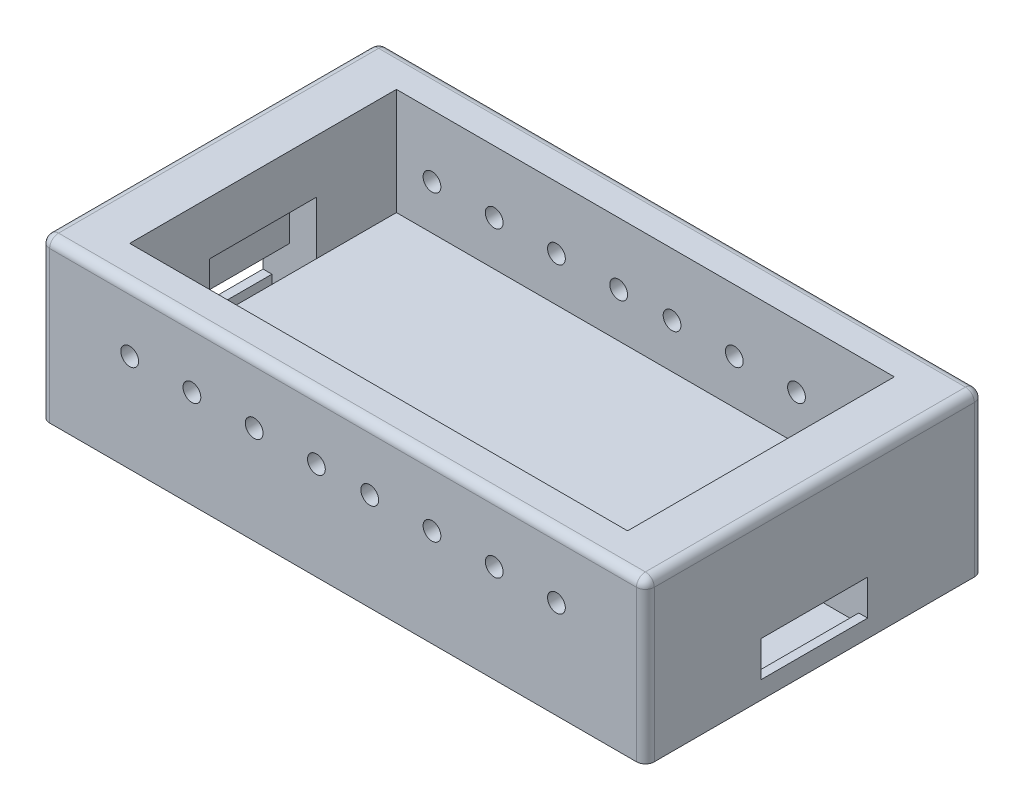
SolidWorks part; units mm, degrees
ref_plane "Front Plane" through (0, 0, 0) normal (0, 0, 1) x (1, 0, 0)
ref_plane "Top Plane" through (0, 0, 0) normal (0, 1, 0) x (1, 0, 0)
ref_plane "Right Plane" through (0, 0, 0) normal (1, 0, 0) x (0, 0, -1)
sketch "Sketch1" plane through (0, 0, 0) normal (0, 1, 0) x (1, 0, 0)
  line L1 (-711.2, 381) -> (711.2, 381)
  line L2 (-711.2, 381) -> (-711.2, -381)
  line L3 (-711.2, -381) -> (711.2, -381)
  line L4 (711.2, 381) -> (711.2, -381)
  line L5 (-863.6, 482.6) -> (863.6, 482.6)
  line L6 (-863.6, 482.6) -> (-863.6, -482.6)
  line L7 (-863.6, -482.6) -> (863.6, -482.6)
  line L8 (863.6, 482.6) -> (863.6, -482.6)
  point P4 (0, 381)
  point P8 (-711.2, 0)
  dimension "D1" = 762
  dimension "D2" = 1422.4
  dimension "D3" = 152.4
  dimension "D4" = 152.4
  dimension "D5" = 101.6
  dimension "D6" = 101.6
extrude "Boss-Extrude1" add sketch "Sketch1" along normal blind 457.2
sketch "Sketch2" plane through (0, 0, 0) normal (0, 1, 0) x (1, 0, 0)
  line L1 (-711.2, 381) -> (711.2, 381)
  line L2 (-711.2, 381) -> (-711.2, -381)
  line L3 (-711.2, -381) -> (711.2, -381)
  line L4 (711.2, 381) -> (711.2, -381)
extrude "Boss-Extrude2" add sketch "Sketch2" along normal blind 152.4
sketch "Sketch3" plane through (0, 152.4, 0) normal (0, 1, 0) x (1, 0, 0)
  line L0 (0, 381) -> (0, -381) construction
  line L1 (711.2, 381) -> (-711.2, 381) construction
  line L2 (-711.2, -381) -> (711.2, -381) construction
  circle A0 centre (0, 0) radius 152.4 construction
sketch "Sketch4" plane through (0, 0, 482.6) normal (0, 0, 1) x (1, 0, 0)
  line L0 (-863.6, 457.2) -> (-863.6, 0) construction
  line L1 (863.6, 457.2) -> (863.6, 0) construction
  line L2 (-863.6, 457.2) -> (863.6, 457.2) construction
  circle A0 centre (-609.6, 279.4) radius 25.4
  circle A1 centre (-431.8, 279.4) radius 25.4
  circle A2 centre (-254, 279.4) radius 25.4
  circle A3 centre (-76.2, 279.4) radius 25.4
  circle A4 centre (76.2, 279.4) radius 25.4
  circle A5 centre (254, 279.4) radius 25.4
  circle A6 centre (431.8, 279.4) radius 25.4
  circle A7 centre (609.6, 279.4) radius 25.4
  dimension "D9" = 50.8
  dimension "D10" = 50.8
  dimension "D11" = 50.8
  dimension "D12" = 50.8
  dimension "D13" = 50.8
  dimension "D14" = 50.8
  dimension "D15" = 50.8
  dimension "D16" = 50.8
  dimension "D1" = 254
  dimension "D2" = 254
  dimension "D3" = 431.8
  dimension "D4" = 431.8
  dimension "D5" = 609.6
  dimension "D6" = 609.6
  dimension "D7" = 787.4
  dimension "D8" = 787.4
  dimension "D17" = 177.8
extrude "Cut-Extrude1" cut sketch "Sketch4" against normal through all both and the other way through all
sketch "Sketch7" plane through (863.6, 0, 0) normal (1, 0, 0) x (0, 0, -1)
  line L1 (-152.4, 25.4) -> (152.4, 25.4)
  line L2 (-152.4, 25.4) -> (-152.4, 152.4)
  line L3 (-152.4, 152.4) -> (152.4, 152.4)
  line L4 (152.4, 25.4) -> (152.4, 152.4)
  line L6 (-482.6, 0) -> (482.6, 0) construction
  point P8 (0, 152.4)
  dimension "D1" = 304.8
  dimension "D2" = 127
  dimension "D3" = 25.4
extrude "Cut-Extrude2" cut sketch "Sketch7" against normal blind 127
sketch "Sketch8" plane through (0, 25.4, 0) normal (0, 1, 0) x (1, 0, 0)
  line L0 (711.2, -381) -> (711.2, 381) construction
  line L1 (711.2, 152.4) -> (787.4, 152.4)
  line L2 (711.2, 152.4) -> (711.2, -152.4)
  line L3 (711.2, -152.4) -> (787.4, -152.4)
  line L4 (787.4, 152.4) -> (787.4, -152.4)
  point P6 (787.4, 0)
  dimension "D1" = 304.8
  dimension "D2" = 76.2
extrude "Cut-Extrude3" cut sketch "Sketch8" along normal blind 304.8
sketch "Sketch9" plane through (0, 25.4, 0) normal (0, 1, 0) x (1, 0, 0)
  line L0 (863.6, -482.6) -> (863.6, 482.6) construction
  line L1 (863.6, 152.4) -> (838.2, 152.4)
  line L2 (863.6, 152.4) -> (863.6, -152.4)
  line L3 (863.6, -152.4) -> (838.2, -152.4)
  line L4 (838.2, 152.4) -> (838.2, -152.4)
  point P6 (838.2, 0)
  dimension "D1" = 304.8
  dimension "D2" = 25.4
extrude "Boss-Extrude3" add sketch "Sketch9" along normal blind 25.4
sketch "Sketch11" plane through (-863.6, 0, 0) normal (-1, 0, 0) x (0, 0, 1)
  line L0 (-482.6, 0) -> (482.6, 0) construction
  line L1 (-152.4, 25.4) -> (152.4, 25.4)
  line L2 (-152.4, 25.4) -> (-152.4, 152.4)
  line L3 (-152.4, 152.4) -> (152.4, 152.4)
  line L4 (152.4, 25.4) -> (152.4, 152.4)
  point P4 (0, 152.4)
  dimension "D1" = 127
  dimension "D2" = 304.8
  dimension "D3" = 25.4
extrude "Cut-Extrude5" cut sketch "Sketch11" against normal blind 127
sketch "Sketch13" plane through (0, 25.4, 0) normal (0, 1, 0) x (1, 0, 0)
  line L0 (-863.6, 482.6) -> (-863.6, -482.6) construction
  line L1 (-863.6, 152.4) -> (-838.2, 152.4)
  line L2 (-863.6, 152.4) -> (-863.6, -152.4)
  line L3 (-863.6, -152.4) -> (-838.2, -152.4)
  line L4 (-838.2, 152.4) -> (-838.2, -152.4)
  point P6 (-838.2, 0)
  dimension "D1" = 304.8
  dimension "D2" = 25.4
extrude "Boss-Extrude4" add sketch "Sketch13" along normal blind 25.4
sketch "Sketch14" plane through (0, 25.4, 0) normal (0, 1, 0) x (1, 0, 0)
  line L0 (-711.2, 381) -> (-711.2, -381) construction
  line L1 (-711.2, 152.4) -> (-787.4, 152.4)
  line L2 (-711.2, 152.4) -> (-711.2, -152.4)
  line L3 (-711.2, -152.4) -> (-787.4, -152.4)
  line L4 (-787.4, 152.4) -> (-787.4, -152.4)
  point P6 (-787.4, 0)
  dimension "D1" = 76.2
  dimension "D2" = 304.8
extrude "Cut-Extrude7" cut sketch "Sketch14" along normal blind 279.4
fillet "Fillet1" radius 25.4 4 edges at (863.6, 457.2, 0) (0, 457.2, -482.6) (-863.6, 457.2, 0) (0, 457.2, 482.6)
fillet "Fillet2" radius 25.4 8 edges at (-856.1605, 449.7605, -475.1605) (856.1605, 449.7605, -475.1605) (856.1605, 449.7605, 475.1605) (-856.1605, 449.7605, 475.1605) (-863.6, 215.9, -482.6) (863.6, 215.9, -482.6) (863.6, 215.9, 482.6) (-863.6, 215.9, 482.6)
